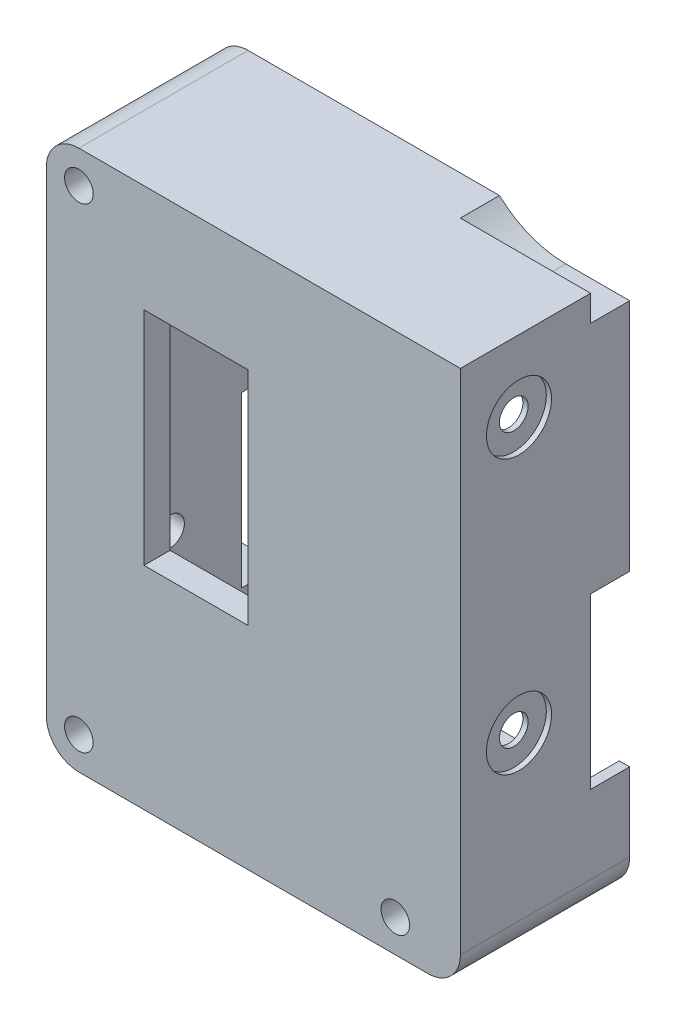
SolidWorks part; units mm, degrees
material "ABS"
ref_plane "正面" through (0, 0, 0) normal (0, 0, 1) x (1, 0, 0)
ref_plane "平面" through (0, 0, 0) normal (0, 1, 0) x (1, 0, 0)
ref_plane "右側面" through (0, 0, 0) normal (1, 0, 0) x (0, 0, -1)
sketch "ｽｹｯﾁ1" plane through (0, 0, 0) normal (0, 0, 1) x (1, 0, 0)
  line L0 (0, 9) -> (26, 9) construction
  line L1 (0, 0) -> (26, 0)
  line L2 (0, 0) -> (0, 32.5)
  line L3 (0, 32.5) -> (26, 32.5)
  line L4 (26, 0) -> (26, 32.5)
  line L5 (26.8, 35.5) -> (26.8, -3.5)
  line L6 (24.3, -6) -> (-2.5, -6)
  line L7 (-5, -3.5) -> (-5, 33)
  line L8 (-2.5, 35.5) -> (26.8, 35.5)
  line L9 (-2.5, 35.5) -> (-2.5, -6) construction
  line L10 (-5, 33) -> (26.8, 33) construction
  line L11 (-5, -3.5) -> (26.8, -3.5) construction
  circle A8 centre (-2.5, 33) radius 1.1
  circle A9 centre (-2.5, -3.5) radius 1.1
  circle A10 centre (21.8, -3.5) radius 1.1
  arc A11 (26.8, -3.5) -> (24.3, -6) centre (24.3, -3.5) cw
  arc A12 (-5, -3.5) -> (-2.5, -6) centre (-2.5, -3.5) ccw
  arc A13 (-5, 33) -> (-2.5, 35.5) centre (-2.5, 33) cw
  dimension "D8" = 2.5
  dimension "D9" = 2.5
  dimension "D11" = 2.2
  dimension "D13" = 2.5
  dimension "D1" = 32.5
  dimension "D2" = 9
  dimension "D3" = 26
  dimension "D4" = 0.8
  dimension "D5" = 6
  dimension "D6" = 5
  dimension "D7" = 3
  dimension "D10" = 2.5
  dimension "D12" = 5
extrude "ﾎﾞｽ - 押し出し1" add sketch "ｽｹｯﾁ1" along normal blind 11
sketch "ｽｹｯﾁ3" plane through (0, 0, 11) normal (0, 0, -1) x (-1, 0, 0)
  line L4 (5, -3.5) -> (5, 33)
  line L5 (2.5, 35.5) -> (-26.8, 35.5)
  line L6 (-26.8, 35.5) -> (-26.8, -3.5)
  line L7 (-24.3, -6) -> (2.5, -6)
  line L8 (5, -3.5) -> (5, 33)
  line L9 (2.5, 35.5) -> (-26.8, 35.5)
  line L10 (-26.8, 35.5) -> (-26.8, -3.5)
  line L11 (-24.3, -6) -> (2.5, -6)
  arc A4 (-26.8, -3.5) -> (-24.3, -6) centre (-24.3, -3.5) ccw
  arc A5 (-26.8, -3.5) -> (-24.3, -6) centre (-24.3, -3.5) ccw
  arc A6 (2.5, -6) -> (5, -3.5) centre (2.5, -3.5) ccw
  arc A7 (2.5, -6) -> (5, -3.5) centre (2.5, -3.5) ccw
  circle A16 centre (-21.8, -3.5) radius 1.1 construction
  circle A17 centre (2.5, -3.5) radius 1.1 construction
  circle A18 centre (2.5, 33) radius 1.1 construction
  arc A19 (5, 33) -> (2.5, 35.5) centre (2.5, 33) ccw
  arc A20 (5, 33) -> (2.5, 35.5) centre (2.5, 33) ccw
  circle A21 centre (-21.8, -3.5) radius 1.1
  circle A22 centre (2.5, -3.5) radius 1.1
  circle A23 centre (2.5, 33) radius 1.1
  dimension "D1" = 0
extrude "ﾎﾞｽ - 押し出し2" add sketch "ｽｹｯﾁ3" against normal blind 2
sketch "ｽｹｯﾁ2" plane through (-5, 0, 0) normal (-1, 0, 0) x (0, 0, 1)
  line L0 (8.5, 43.5506) -> (8.5, -12.0222) construction
  line L6 (13, 0) -> (13, 32.5) construction
  line L8 (11, 32.5) -> (0, 32.5) construction
  circle A0 centre (8.5, 30) radius 1.1
  circle A1 centre (8.5, 9) radius 1.1
  dimension "D2" = 2.5
  dimension "D4" = 2.2
  dimension "D1" = 4.5
  dimension "D3" = 21
extrude "ｶｯﾄ - 押し出し1" cut sketch "ｽｹｯﾁ2" against normal through all
sketch "ｽｹｯﾁ4" plane through (0, 0, 13) normal (0, 0, 1) x (1, 0, 0)
  line L0 (26, 16.25) -> (0, 16.25) construction
  line L1 (10.5, 10.25) -> (2.5, 10.25)
  line L2 (10.5, 10.25) -> (10.5, 27.25)
  line L3 (10.5, 27.25) -> (2.5, 27.25)
  line L12 (2.5, 10.25) -> (2.5, 27.25)
  line L23 (0, 32.5) -> (0, 0)
  line L33 (26, 32.5) -> (0, 32.5)
  line L34 (26, 0) -> (26, 32.5)
  line L35 (0, 0) -> (26, 0)
  line L36 (0, 32.5) -> (0, 0) construction
  line L37 (26, 32.5) -> (0, 32.5) construction
  line L38 (26, 0) -> (26, 32.5) construction
  line L39 (0, 0) -> (26, 0) construction
  dimension "D2" = 2.5
  dimension "D3" = 8
  dimension "D4" = 6
  dimension "D5" = 11
  dimension "D1" = 0
extrude "ｶｯﾄ - 押し出し3" cut sketch "ｽｹｯﾁ4" against normal blind 10
sketch "ｽｹｯﾁ5" plane through (26.8, 0, 0) normal (1, 0, 0) x (0, 0, -1)
  circle A0 centre (-8.5, 30) radius 2.5
  circle A1 centre (-8.5, 9) radius 2.5
  dimension "D1" = 5
  dimension "D2" = 5
extrude "ｶｯﾄ - 押し出し4" cut sketch "ｽｹｯﾁ5" against normal blind 0.4
sketch "ｽｹｯﾁ6" plane through (0, 0, 0) normal (0, 0, -1) x (-1, 0, 0)
  line L5 (0, 32.5) -> (0, 0) construction
  line L6 (0, 15.5) -> (3.5, 15.5)
  line L7 (0, 15.5) -> (0, 2.5)
  line L8 (0, 2.5) -> (3.5, 2.5)
  line L9 (3.5, 15.5) -> (3.5, 2.5)
  line L10 (0, 9) -> (3.5, 9) construction
  line L11 (0, 0) -> (-26, 0) construction
  line L13 (-26.8, 35.5) -> (-16.8, 35.5)
  line L14 (-26.8, 35.5) -> (-26.8, 33.5)
  line L15 (-26.8, 33.5) -> (-16.8, 33.5)
  line L16 (-16.8, 35.5) -> (-16.8, 33.5)
  dimension "D1" = 10
  dimension "D2" = 2
  dimension "D3" = 13
  dimension "D4" = 9
  dimension "D5" = 3.5
extrude "ｶｯﾄ - 押し出し6" cut sketch "ｽｹｯﾁ6" against normal blind 3
fillet "ﾌｨﾚｯﾄ1" radius 7.5 1 edges at (16.8, 33.5, 1.5)
sketch "ｽｹｯﾁ7" plane through (-3.5, 0, 0) normal (1, 0, 0) x (0, 0, -1)
  line L4 (0, 2.5) -> (0, 15.5)
  line L5 (0, 15.5) -> (-3, 15.5)
  line L6 (-3, 15.5) -> (-3, 2.5)
  line L7 (-3, 2.5) -> (0, 2.5)
  line L8 (0, 2.5) -> (0, 15.5)
  line L9 (0, 15.5) -> (-3, 15.5)
  line L10 (-3, 15.5) -> (-3, 2.5)
  line L11 (-3, 2.5) -> (0, 2.5)
  dimension "D1" = 0
extrude "ｶｯﾄ - 押し出し7" cut sketch "ｽｹｯﾁ7" along normal through all
